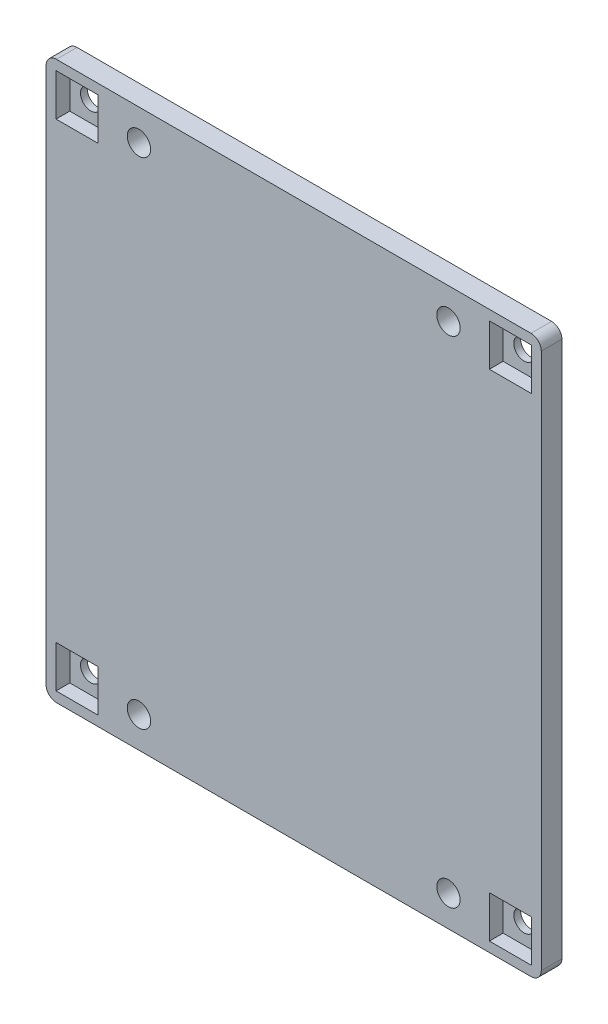
SolidWorks part; units mm, degrees
ref_plane "Alzado" through (0, 0, 0) normal (0, 0, 1) x (1, 0, 0)
ref_plane "Planta" through (0, 0, 0) normal (0, 1, 0) x (1, 0, 0)
ref_plane "Vista lateral" through (0, 0, 0) normal (1, 0, 0) x (0, 0, -1)
sketch "Model" plane through (0, 0, 0) normal (0, 0, 1) x (1, 0, 0)
  line L0 (6.1877, 221.4099) -> (6.1877, 299.4145)
  line L1 (7.6877, 300.9145) -> (76.6901, 300.9145)
  line L2 (78.1901, 299.4145) -> (78.1901, 221.4099)
  line L3 (76.6901, 219.9099) -> (7.6877, 219.9099)
  arc A0 (78.1901, 299.4145) -> (76.6901, 300.9145) centre (76.6901, 299.4145) ccw
  arc A1 (76.6901, 219.9099) -> (78.1901, 221.4099) centre (76.6901, 221.4099) ccw
  arc A2 (6.1877, 221.4099) -> (7.6877, 219.9099) centre (7.6877, 221.4099) ccw
  arc A3 (7.6877, 300.9145) -> (6.1877, 299.4145) centre (7.6877, 299.4145) ccw
  circle A4 centre (73.6901, 224.4096) radius 1.5
  circle A5 centre (10.6874, 296.4145) radius 1.5
  circle A6 centre (10.6874, 224.4096) radius 1.5
  circle A7 centre (73.6901, 296.4145) radius 1.5
  circle A8 centre (19.687, 296.4145) radius 1.7
  circle A9 centre (64.6904, 296.4145) radius 1.7
  circle A10 centre (19.687, 224.4096) radius 1.7
  circle A11 centre (64.6904, 224.4096) radius 1.7
extrude "Saliente-Extruir1" add sketch "Model" along normal blind 3
sketch "Croquis2" plane through (0, 0, 3) normal (0, 0, 1) x (1, 0, 0)
  line L1 (7.6374, 299.4645) -> (13.7374, 299.4645)
  line L2 (7.6374, 299.4645) -> (7.6374, 293.3645)
  line L3 (7.6374, 293.3645) -> (13.7374, 293.3645)
  line L4 (13.7374, 299.4645) -> (13.7374, 293.3645)
  line L5 (7.6374, 299.4645) -> (13.7374, 293.3645) construction
  line L6 (7.6374, 293.3645) -> (13.7374, 299.4645) construction
  line L7 (70.6401, 299.4645) -> (76.7401, 299.4645)
  line L8 (70.6401, 299.4645) -> (70.6401, 293.3645)
  line L9 (70.6401, 293.3645) -> (76.7401, 293.3645)
  line L10 (76.7401, 299.4645) -> (76.7401, 293.3645)
  line L11 (70.6401, 299.4645) -> (76.7401, 293.3645) construction
  line L12 (70.6401, 293.3645) -> (76.7401, 299.4645) construction
  line L13 (70.6401, 227.4596) -> (76.7401, 227.4596)
  line L14 (70.6401, 227.4596) -> (70.6401, 221.3596)
  line L15 (70.6401, 221.3596) -> (76.7401, 221.3596)
  line L16 (76.7401, 227.4596) -> (76.7401, 221.3596)
  line L17 (70.6401, 227.4596) -> (76.7401, 221.3596) construction
  line L18 (70.6401, 221.3596) -> (76.7401, 227.4596) construction
  line L19 (13.7374, 221.3596) -> (7.6374, 221.3596)
  line L20 (13.7374, 221.3596) -> (13.7374, 227.4596)
  line L21 (13.7374, 227.4596) -> (7.6374, 227.4596)
  line L22 (7.6374, 221.3596) -> (7.6374, 227.4596)
  line L23 (13.7374, 221.3596) -> (7.6374, 227.4596) construction
  line L24 (13.7374, 227.4596) -> (7.6374, 221.3596) construction
  point P0 (10.6874, 296.4145)
  point P5 (73.6901, 296.4145)
  point P11 (73.6901, 224.4096)
  point P17 (10.6874, 224.4096)
  dimension "D1" = 6.1
  dimension "D2" = 6.1
  dimension "D3" = 6.1
  dimension "D4" = 6.1
  dimension "D5" = 6.1
  dimension "D6" = 6.1
  dimension "D7" = 6.1
  dimension "D8" = 6.1
extrude "Cortar-Extruir1" cut sketch "Croquis2" against normal blind 2
